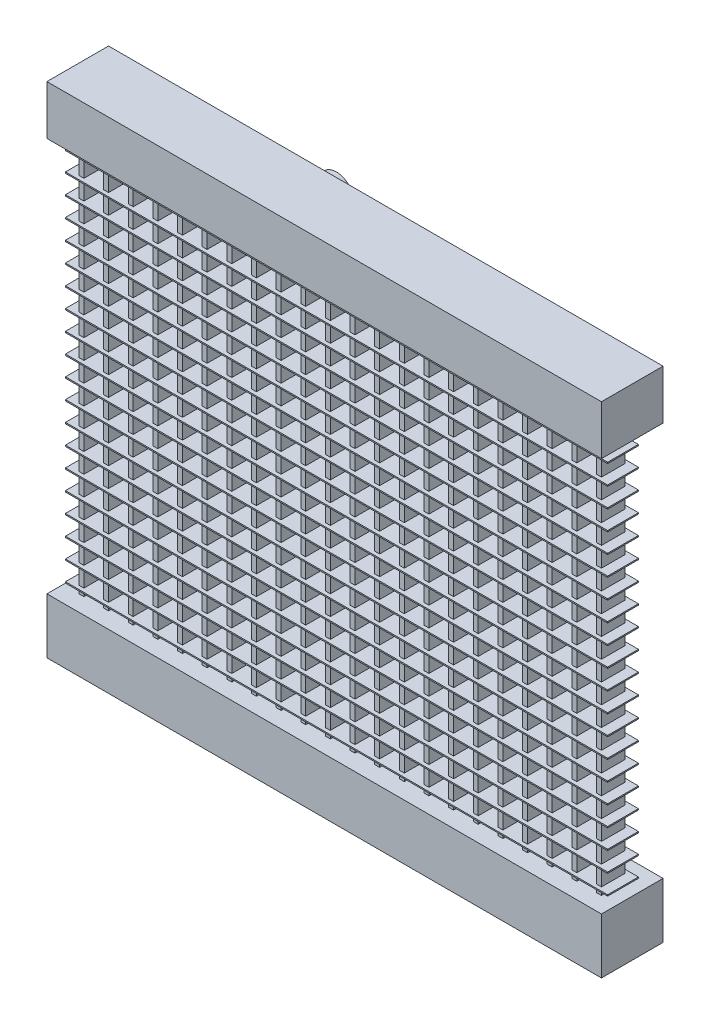
SolidWorks part; units mm, degrees
ref_plane "Front Plane" through (0, 0, 0) normal (0, 0, 1) x (1, 0, 0)
ref_plane "Top Plane" through (0, 0, 0) normal (0, 1, 0) x (1, 0, 0)
ref_plane "Right Plane" through (0, 0, 0) normal (1, 0, 0) x (0, 0, -1)
sketch "Sketch1" plane through (0, 0, 0) normal (0, 0, 1) x (1, 0, 0)
  line L1 (-225, 40) -> (225, 40)
  line L2 (-225, 40) -> (-225, 85)
  line L3 (-225, 85) -> (225, 85)
  line L4 (225, 40) -> (225, 85)
extrude "Liquid_header_ENVELOPE_NO_INTERNAL_CIRCUITING" add sketch "Sketch1" along normal blind 50 from offset 285 separate body
sketch "Sketch2" plane through (0, 0, 0) normal (0, 0, 1) x (1, 0, 0)
  line L1 (-225, 405) -> (225, 405)
  line L2 (-225, 405) -> (-225, 445)
  line L3 (-225, 445) -> (225, 445)
  line L4 (225, 405) -> (225, 445)
extrude "Vapour_header_ENVELOPE_NO_INTERNAL_CIRCUITING" add sketch "Sketch2" along normal blind 50 from offset 285 separate body
sketch "Sketch3" plane through (0, 0, 0) normal (0, 0, 1) x (1, 0, 0)
  line L1 (-212, 85) -> (-208, 85)
  line L2 (-212, 85) -> (-212, 405)
  line L3 (-212, 405) -> (-208, 405)
  line L4 (-208, 85) -> (-208, 405)
extrude "Refrigerant_tube_VISUAL_ENVELOPE" add sketch "Sketch3" along normal blind 19 from offset 303 separate body
sketch "Sketch4" plane through (0, 0, 0) normal (0, 0, 1) x (1, 0, 0)
  line L1 (-192, 85) -> (-188, 85)
  line L2 (-192, 85) -> (-192, 405)
  line L3 (-192, 405) -> (-188, 405)
  line L4 (-188, 85) -> (-188, 405)
extrude "Boss-Extrude4" add sketch "Sketch4" along normal blind 19 from offset 303 separate body
sketch "Sketch5" plane through (0, 0, 0) normal (0, 0, 1) x (1, 0, 0)
  line L1 (-172, 85) -> (-168, 85)
  line L2 (-172, 85) -> (-172, 405)
  line L3 (-172, 405) -> (-168, 405)
  line L4 (-168, 85) -> (-168, 405)
extrude "Boss-Extrude5" add sketch "Sketch5" along normal blind 19 from offset 303 separate body
sketch "Sketch6" plane through (0, 0, 0) normal (0, 0, 1) x (1, 0, 0)
  line L1 (-152, 85) -> (-148, 85)
  line L2 (-152, 85) -> (-152, 405)
  line L3 (-152, 405) -> (-148, 405)
  line L4 (-148, 85) -> (-148, 405)
extrude "Boss-Extrude6" add sketch "Sketch6" along normal blind 19 from offset 303 separate body
sketch "Sketch7" plane through (0, 0, 0) normal (0, 0, 1) x (1, 0, 0)
  line L1 (-132, 85) -> (-128, 85)
  line L2 (-132, 85) -> (-132, 405)
  line L3 (-132, 405) -> (-128, 405)
  line L4 (-128, 85) -> (-128, 405)
extrude "Boss-Extrude7" add sketch "Sketch7" along normal blind 19 from offset 303 separate body
sketch "Sketch8" plane through (0, 0, 0) normal (0, 0, 1) x (1, 0, 0)
  line L1 (-112, 85) -> (-108, 85)
  line L2 (-112, 85) -> (-112, 405)
  line L3 (-112, 405) -> (-108, 405)
  line L4 (-108, 85) -> (-108, 405)
extrude "Boss-Extrude8" add sketch "Sketch8" along normal blind 19 from offset 303 separate body
sketch "Sketch9" plane through (0, 0, 0) normal (0, 0, 1) x (1, 0, 0)
  line L1 (-92, 85) -> (-88, 85)
  line L2 (-92, 85) -> (-92, 405)
  line L3 (-92, 405) -> (-88, 405)
  line L4 (-88, 85) -> (-88, 405)
extrude "Boss-Extrude9" add sketch "Sketch9" along normal blind 19 from offset 303 separate body
sketch "Sketch10" plane through (0, 0, 0) normal (0, 0, 1) x (1, 0, 0)
  line L1 (-72, 85) -> (-68, 85)
  line L2 (-72, 85) -> (-72, 405)
  line L3 (-72, 405) -> (-68, 405)
  line L4 (-68, 85) -> (-68, 405)
extrude "Boss-Extrude10" add sketch "Sketch10" along normal blind 19 from offset 303 separate body
sketch "Sketch11" plane through (0, 0, 0) normal (0, 0, 1) x (1, 0, 0)
  line L1 (-52, 85) -> (-48, 85)
  line L2 (-52, 85) -> (-52, 405)
  line L3 (-52, 405) -> (-48, 405)
  line L4 (-48, 85) -> (-48, 405)
extrude "Boss-Extrude11" add sketch "Sketch11" along normal blind 19 from offset 303 separate body
sketch "Sketch12" plane through (0, 0, 0) normal (0, 0, 1) x (1, 0, 0)
  line L1 (-32, 85) -> (-28, 85)
  line L2 (-32, 85) -> (-32, 405)
  line L3 (-32, 405) -> (-28, 405)
  line L4 (-28, 85) -> (-28, 405)
extrude "Boss-Extrude12" add sketch "Sketch12" along normal blind 19 from offset 303 separate body
sketch "Sketch13" plane through (0, 0, 0) normal (0, 0, 1) x (1, 0, 0)
  line L1 (-12, 85) -> (-8, 85)
  line L2 (-12, 85) -> (-12, 405)
  line L3 (-12, 405) -> (-8, 405)
  line L4 (-8, 85) -> (-8, 405)
extrude "Boss-Extrude13" add sketch "Sketch13" along normal blind 19 from offset 303 separate body
sketch "Sketch14" plane through (0, 0, 0) normal (0, 0, 1) x (1, 0, 0)
  line L1 (8, 85) -> (12, 85)
  line L2 (8, 85) -> (8, 405)
  line L3 (8, 405) -> (12, 405)
  line L4 (12, 85) -> (12, 405)
extrude "Boss-Extrude14" add sketch "Sketch14" along normal blind 19 from offset 303 separate body
sketch "Sketch15" plane through (0, 0, 0) normal (0, 0, 1) x (1, 0, 0)
  line L1 (28, 85) -> (32, 85)
  line L2 (28, 85) -> (28, 405)
  line L3 (28, 405) -> (32, 405)
  line L4 (32, 85) -> (32, 405)
extrude "Boss-Extrude15" add sketch "Sketch15" along normal blind 19 from offset 303 separate body
sketch "Sketch16" plane through (0, 0, 0) normal (0, 0, 1) x (1, 0, 0)
  line L1 (48, 85) -> (52, 85)
  line L2 (48, 85) -> (48, 405)
  line L3 (48, 405) -> (52, 405)
  line L4 (52, 85) -> (52, 405)
extrude "Boss-Extrude16" add sketch "Sketch16" along normal blind 19 from offset 303 separate body
sketch "Sketch17" plane through (0, 0, 0) normal (0, 0, 1) x (1, 0, 0)
  line L1 (68, 85) -> (72, 85)
  line L2 (68, 85) -> (68, 405)
  line L3 (68, 405) -> (72, 405)
  line L4 (72, 85) -> (72, 405)
extrude "Boss-Extrude17" add sketch "Sketch17" along normal blind 19 from offset 303 separate body
sketch "Sketch18" plane through (0, 0, 0) normal (0, 0, 1) x (1, 0, 0)
  line L1 (88, 85) -> (92, 85)
  line L2 (88, 85) -> (88, 405)
  line L3 (88, 405) -> (92, 405)
  line L4 (92, 85) -> (92, 405)
extrude "Boss-Extrude18" add sketch "Sketch18" along normal blind 19 from offset 303 separate body
sketch "Sketch19" plane through (0, 0, 0) normal (0, 0, 1) x (1, 0, 0)
  line L1 (108, 85) -> (112, 85)
  line L2 (108, 85) -> (108, 405)
  line L3 (108, 405) -> (112, 405)
  line L4 (112, 85) -> (112, 405)
extrude "Boss-Extrude19" add sketch "Sketch19" along normal blind 19 from offset 303 separate body
sketch "Sketch20" plane through (0, 0, 0) normal (0, 0, 1) x (1, 0, 0)
  line L1 (128, 85) -> (132, 85)
  line L2 (128, 85) -> (128, 405)
  line L3 (128, 405) -> (132, 405)
  line L4 (132, 85) -> (132, 405)
extrude "Boss-Extrude20" add sketch "Sketch20" along normal blind 19 from offset 303 separate body
sketch "Sketch21" plane through (0, 0, 0) normal (0, 0, 1) x (1, 0, 0)
  line L1 (148, 85) -> (152, 85)
  line L2 (148, 85) -> (148, 405)
  line L3 (148, 405) -> (152, 405)
  line L4 (152, 85) -> (152, 405)
extrude "Boss-Extrude21" add sketch "Sketch21" along normal blind 19 from offset 303 separate body
sketch "Sketch22" plane through (0, 0, 0) normal (0, 0, 1) x (1, 0, 0)
  line L1 (168, 85) -> (172, 85)
  line L2 (168, 85) -> (168, 405)
  line L3 (168, 405) -> (172, 405)
  line L4 (172, 85) -> (172, 405)
extrude "Boss-Extrude22" add sketch "Sketch22" along normal blind 19 from offset 303 separate body
sketch "Sketch23" plane through (0, 0, 0) normal (0, 0, 1) x (1, 0, 0)
  line L1 (188, 85) -> (192, 85)
  line L2 (188, 85) -> (188, 405)
  line L3 (188, 405) -> (192, 405)
  line L4 (192, 85) -> (192, 405)
extrude "Boss-Extrude23" add sketch "Sketch23" along normal blind 19 from offset 303 separate body
sketch "Sketch24" plane through (0, 0, 0) normal (0, 0, 1) x (1, 0, 0)
  line L1 (208, 85) -> (212, 85)
  line L2 (208, 85) -> (208, 405)
  line L3 (208, 405) -> (212, 405)
  line L4 (212, 85) -> (212, 405)
extrude "Boss-Extrude24" add sketch "Sketch24" along normal blind 19 from offset 303 separate body
sketch "Sketch25" plane through (0, 0, 0) normal (0, 0, 1) x (1, 0, 0)
  line L1 (-220, 90) -> (220, 90)
  line L2 (-220, 90) -> (-220, 91)
  line L3 (-220, 91) -> (220, 91)
  line L4 (220, 90) -> (220, 91)
extrude "Air_fin_SIMPLIFIED" add sketch "Sketch25" along normal blind 25 from offset 300 separate body
sketch "Sketch26" plane through (0, 0, 0) normal (0, 0, 1) x (1, 0, 0)
  line L1 (-220, 106) -> (220, 106)
  line L2 (-220, 106) -> (-220, 107)
  line L3 (-220, 107) -> (220, 107)
  line L4 (220, 106) -> (220, 107)
extrude "Boss-Extrude26" add sketch "Sketch26" along normal blind 25 from offset 300 separate body
sketch "Sketch27" plane through (0, 0, 0) normal (0, 0, 1) x (1, 0, 0)
  line L1 (-220, 122) -> (220, 122)
  line L2 (-220, 122) -> (-220, 123)
  line L3 (-220, 123) -> (220, 123)
  line L4 (220, 122) -> (220, 123)
extrude "Boss-Extrude27" add sketch "Sketch27" along normal blind 25 from offset 300 separate body
sketch "Sketch28" plane through (0, 0, 0) normal (0, 0, 1) x (1, 0, 0)
  line L1 (-220, 138) -> (220, 138)
  line L2 (-220, 138) -> (-220, 139)
  line L3 (-220, 139) -> (220, 139)
  line L4 (220, 138) -> (220, 139)
extrude "Boss-Extrude28" add sketch "Sketch28" along normal blind 25 from offset 300 separate body
sketch "Sketch29" plane through (0, 0, 0) normal (0, 0, 1) x (1, 0, 0)
  line L1 (-220, 154) -> (220, 154)
  line L2 (-220, 154) -> (-220, 155)
  line L3 (-220, 155) -> (220, 155)
  line L4 (220, 154) -> (220, 155)
extrude "Boss-Extrude29" add sketch "Sketch29" along normal blind 25 from offset 300 separate body
sketch "Sketch30" plane through (0, 0, 0) normal (0, 0, 1) x (1, 0, 0)
  line L1 (-220, 170) -> (220, 170)
  line L2 (-220, 170) -> (-220, 171)
  line L3 (-220, 171) -> (220, 171)
  line L4 (220, 170) -> (220, 171)
extrude "Boss-Extrude30" add sketch "Sketch30" along normal blind 25 from offset 300 separate body
sketch "Sketch31" plane through (0, 0, 0) normal (0, 0, 1) x (1, 0, 0)
  line L1 (-220, 186) -> (220, 186)
  line L2 (-220, 186) -> (-220, 187)
  line L3 (-220, 187) -> (220, 187)
  line L4 (220, 186) -> (220, 187)
extrude "Boss-Extrude31" add sketch "Sketch31" along normal blind 25 from offset 300 separate body
sketch "Sketch32" plane through (0, 0, 0) normal (0, 0, 1) x (1, 0, 0)
  line L1 (-220, 202) -> (220, 202)
  line L2 (-220, 202) -> (-220, 203)
  line L3 (-220, 203) -> (220, 203)
  line L4 (220, 202) -> (220, 203)
extrude "Boss-Extrude32" add sketch "Sketch32" along normal blind 25 from offset 300 separate body
sketch "Sketch33" plane through (0, 0, 0) normal (0, 0, 1) x (1, 0, 0)
  line L1 (-220, 218) -> (220, 218)
  line L2 (-220, 218) -> (-220, 219)
  line L3 (-220, 219) -> (220, 219)
  line L4 (220, 218) -> (220, 219)
extrude "Boss-Extrude33" add sketch "Sketch33" along normal blind 25 from offset 300 separate body
sketch "Sketch34" plane through (0, 0, 0) normal (0, 0, 1) x (1, 0, 0)
  line L1 (-220, 234) -> (220, 234)
  line L2 (-220, 234) -> (-220, 235)
  line L3 (-220, 235) -> (220, 235)
  line L4 (220, 234) -> (220, 235)
extrude "Boss-Extrude34" add sketch "Sketch34" along normal blind 25 from offset 300 separate body
sketch "Sketch35" plane through (0, 0, 0) normal (0, 0, 1) x (1, 0, 0)
  line L1 (-220, 250) -> (220, 250)
  line L2 (-220, 250) -> (-220, 251)
  line L3 (-220, 251) -> (220, 251)
  line L4 (220, 250) -> (220, 251)
extrude "Boss-Extrude35" add sketch "Sketch35" along normal blind 25 from offset 300 separate body
sketch "Sketch36" plane through (0, 0, 0) normal (0, 0, 1) x (1, 0, 0)
  line L1 (-220, 266) -> (220, 266)
  line L2 (-220, 266) -> (-220, 267)
  line L3 (-220, 267) -> (220, 267)
  line L4 (220, 266) -> (220, 267)
extrude "Boss-Extrude36" add sketch "Sketch36" along normal blind 25 from offset 300 separate body
sketch "Sketch37" plane through (0, 0, 0) normal (0, 0, 1) x (1, 0, 0)
  line L1 (-220, 282) -> (220, 282)
  line L2 (-220, 282) -> (-220, 283)
  line L3 (-220, 283) -> (220, 283)
  line L4 (220, 282) -> (220, 283)
extrude "Boss-Extrude37" add sketch "Sketch37" along normal blind 25 from offset 300 separate body
sketch "Sketch38" plane through (0, 0, 0) normal (0, 0, 1) x (1, 0, 0)
  line L1 (-220, 298) -> (220, 298)
  line L2 (-220, 298) -> (-220, 299)
  line L3 (-220, 299) -> (220, 299)
  line L4 (220, 298) -> (220, 299)
extrude "Boss-Extrude38" add sketch "Sketch38" along normal blind 25 from offset 300 separate body
sketch "Sketch39" plane through (0, 0, 0) normal (0, 0, 1) x (1, 0, 0)
  line L1 (-220, 314) -> (220, 314)
  line L2 (-220, 314) -> (-220, 315)
  line L3 (-220, 315) -> (220, 315)
  line L4 (220, 314) -> (220, 315)
extrude "Boss-Extrude39" add sketch "Sketch39" along normal blind 25 from offset 300 separate body
sketch "Sketch40" plane through (0, 0, 0) normal (0, 0, 1) x (1, 0, 0)
  line L1 (-220, 330) -> (220, 330)
  line L2 (-220, 330) -> (-220, 331)
  line L3 (-220, 331) -> (220, 331)
  line L4 (220, 330) -> (220, 331)
extrude "Boss-Extrude40" add sketch "Sketch40" along normal blind 25 from offset 300 separate body
sketch "Sketch41" plane through (0, 0, 0) normal (0, 0, 1) x (1, 0, 0)
  line L1 (-220, 346) -> (220, 346)
  line L2 (-220, 346) -> (-220, 347)
  line L3 (-220, 347) -> (220, 347)
  line L4 (220, 346) -> (220, 347)
extrude "Boss-Extrude41" add sketch "Sketch41" along normal blind 25 from offset 300 separate body
sketch "Sketch42" plane through (0, 0, 0) normal (0, 0, 1) x (1, 0, 0)
  line L1 (-220, 362) -> (220, 362)
  line L2 (-220, 362) -> (-220, 363)
  line L3 (-220, 363) -> (220, 363)
  line L4 (220, 362) -> (220, 363)
extrude "Boss-Extrude42" add sketch "Sketch42" along normal blind 25 from offset 300 separate body
sketch "Sketch43" plane through (0, 0, 0) normal (0, 0, 1) x (1, 0, 0)
  line L1 (-220, 378) -> (220, 378)
  line L2 (-220, 378) -> (-220, 379)
  line L3 (-220, 379) -> (220, 379)
  line L4 (220, 378) -> (220, 379)
extrude "Boss-Extrude43" add sketch "Sketch43" along normal blind 25 from offset 300 separate body
sketch "Sketch44" plane through (0, 0, 0) normal (0, 0, 1) x (1, 0, 0)
  line L1 (-220, 394) -> (220, 394)
  line L2 (-220, 394) -> (-220, 395)
  line L3 (-220, 395) -> (220, 395)
  line L4 (220, 394) -> (220, 395)
extrude "Boss-Extrude44" add sketch "Sketch44" along normal blind 25 from offset 300 separate body
sketch "Sketch45" plane through (0, 0, 0) normal (0, 0, 1) x (1, 0, 0)
  circle A0 centre (-55, 420) radius 14
  circle A1 centre (-55, 420) radius 8
extrude "Vapour_inlet_ID16_POSITION_ASSUMED" add sketch "Sketch45" along normal blind 15 from offset 270 separate body
sketch "Sketch46" plane through (0, 0, 0) normal (0, 0, 1) x (1, 0, 0)
  circle A0 centre (-30, 64) radius 10
  circle A1 centre (-30, 64) radius 3
extrude "Liquid_outlet_ID6_POSITION_ASSUMED" add sketch "Sketch46" along normal blind 15 from offset 270 separate body
